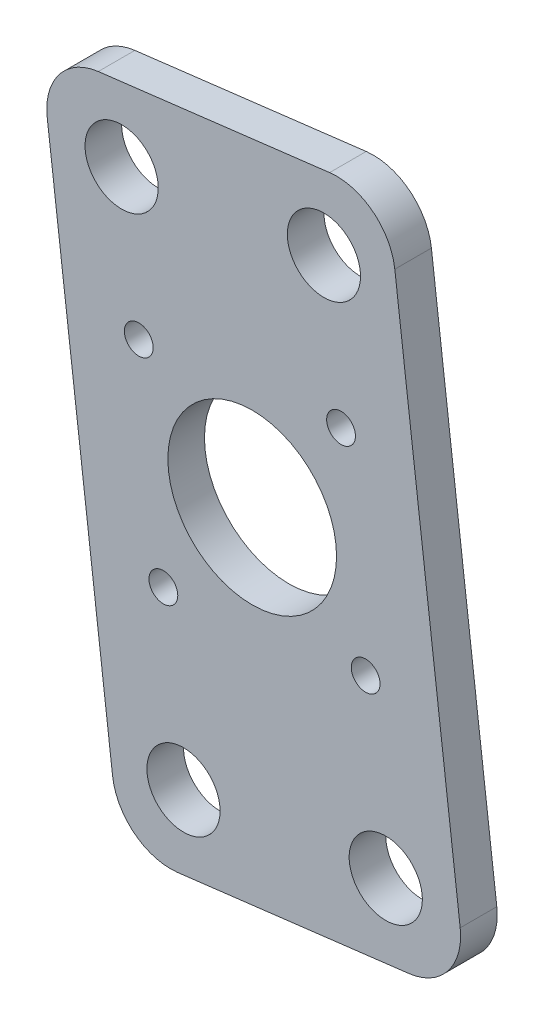
SolidWorks part; units mm, degrees
ref_plane "Front Plane" through (0, 0, 0) normal (0, 0, 1) x (1, 0, 0)
ref_plane "Top Plane" through (0, 0, 0) normal (0, 1, 0) x (1, 0, 0)
ref_plane "Right Plane" through (0, 0, 0) normal (1, 0, 0) x (0, 0, -1)
sketch "Sketch1" plane through (0, 0, 0) normal (0, 0, 1) x (1, 0, 0)
  line L12 (-108.1848, -135.7641) -> (-102.5125, -182.4105)
  line L15 (-96.8564, -186.8401) -> (-76.7866, -184.3996)
  line L16 (-72.3569, -178.7435) -> (-78.0293, -132.0971)
  line L17 (-83.6853, -127.6675) -> (-103.7552, -130.108)
  line L18 (-82.6932, -146.3471) -> (-80.5593, -163.8955) construction
  line L19 (-90.4004, -156.1882) -> (-93.9794, -126.7566) construction
  line L20 (-90.4004, -156.1882) -> (-86.8215, -185.6198) construction
  line L21 (-85.283, -160.196) -> (-85.4799, -160.0418)
  line L22 (-95.321, -152.3346) -> (-95.5178, -152.1805)
  arc A0 (-97.1236, -166.8001) -> (-99.0918, -165.2587) centre (-98.1077, -166.0294) ccw
  arc A1 (-99.0918, -165.2587) -> (-97.1236, -166.8001) centre (-98.1077, -166.0294) ccw
  arc A2 (-81.5434, -163.1247) -> (-79.5752, -164.6662) centre (-80.5593, -163.8955) ccw
  arc A3 (-79.5752, -164.6662) -> (-81.5434, -163.1247) centre (-80.5593, -163.8955) ccw
  arc A4 (-81.7091, -147.1178) -> (-83.6773, -145.5763) centre (-82.6932, -146.3471) ccw
  arc A5 (-83.6773, -145.5763) -> (-81.7091, -147.1178) centre (-82.6932, -146.3471) ccw
  arc A6 (-101.2257, -147.7103) -> (-99.2575, -149.2517) centre (-100.2416, -148.481) ccw
  arc A7 (-99.2575, -149.2517) -> (-101.2257, -147.7103) centre (-100.2416, -148.481) ccw
  circle A25 centre (-101.7279, -136.2583) radius 3.175
  circle A26 centre (-84.1795, -134.1244) radius 3.175
  circle A27 centre (-78.8138, -178.2493) radius 3.175
  circle A28 centre (-96.3622, -180.3832) radius 3.175
  arc A29 (-102.5125, -182.4105) -> (-96.8564, -186.8401) centre (-97.4696, -181.7973) ccw
  arc A30 (-76.7866, -184.3996) -> (-72.3569, -178.7435) centre (-77.3998, -179.3567) ccw
  arc A31 (-78.0293, -132.0971) -> (-83.6853, -127.6675) centre (-83.0721, -132.7103) ccw
  arc A32 (-108.1848, -135.7641) -> (-103.7552, -130.108) centre (-103.1419, -135.1509) cw
  arc A33 (-85.4799, -160.0418) -> (-95.321, -152.3346) centre (-90.4004, -156.1882) ccw
  circle A34 centre (-90.4004, -156.1882) radius 7.3172
  arc A35 (-94.4082, -161.3056) -> (-85.283, -160.196) centre (-90.4004, -156.1882) ccw
  arc A36 (-95.321, -152.3346) -> (-85.4799, -160.0418) centre (-90.4004, -156.1882) ccw
  arc A37 (-95.5178, -152.1805) -> (-94.4082, -161.3056) centre (-90.4004, -156.1882) ccw
  point P32 (0, 0)
  dimension "D6" = 6.35
  dimension "D8" = 6.35
  dimension "D10" = 6.35
  dimension "D15" = 5.08
  dimension "D2" = 6.35
  dimension "D5" = 6.35
  dimension "D7" = 6.35
  dimension "D9" = 6.35
  dimension "D14" = 6.35
  dimension "D1" = 6.35
  dimension "D3" = 6.35
  dimension "D4" = 6.35
  dimension "D11" = 6.35
  dimension "D12" = 6.35
  dimension "D13" = 6.35
extrude "Boss-Extrude2" add sketch "Sketch1" along normal blind 3.175 contours A32 L12 A29 L15 A30 L16 A31 L17 A34 A28 A27 A26 A25 A7 A6 A5 A4 A3 A2 A1 A0 region at (-106.596, -132.4458, 0)
